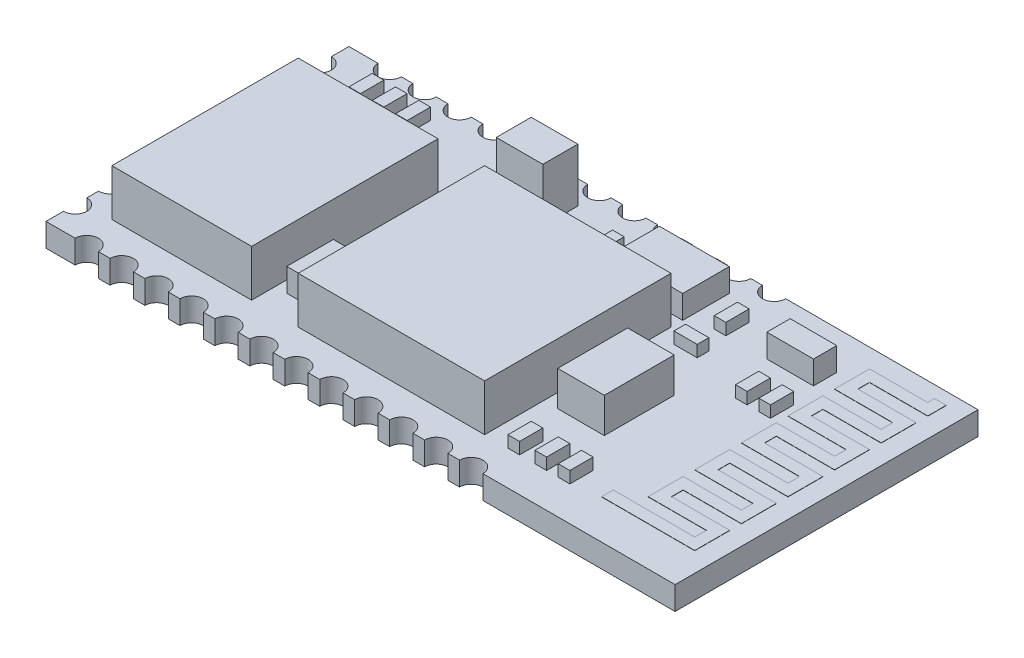
SolidWorks part; units mm, degrees
ref_plane "Front Plane" through (0, 0, 0) normal (0, 0, 1) x (1, 0, 0)
ref_plane "Top Plane" through (0, 0, 0) normal (0, 1, 0) x (1, 0, 0)
ref_plane "Right Plane" through (0, 0, 0) normal (1, 0, 0) x (0, 0, -1)
sketch "Sketch1" plane through (0, 0, 0) normal (0, 1, 0) x (1, 0, 0)
  line L1 (13.5, -6.5) -> (-13.5, -6.5)
  line L2 (13.5, -6.5) -> (13.5, 6.5)
  line L3 (13.5, 6.5) -> (-13.5, 6.5)
  line L4 (-13.5, -6.5) -> (-13.5, 6.5)
  line L5 (13.5, -6.5) -> (-13.5, 6.5) construction
  line L6 (13.5, 6.5) -> (-13.5, -6.5) construction
  point P0 (0, 0)
  dimension "D1" = 13
  dimension "D2" = 27
extrude "Boss-Extrude1" add sketch "Sketch1" along normal blind 1
sketch "Sketch2" plane through (0, 1, 0) normal (0, 1, 0) x (1, 0, 0)
  line L0 (-13.5, 6.5) -> (-13.5, -6.5) construction
  circle A0 centre (-13.5, 5.25) radius 0.5
  circle A1 centre (-13.5, 3.75) radius 0.5
  circle A2 centre (-13.5, 2.25) radius 0.5
  circle A3 centre (-13.5, 0.75) radius 0.5
  circle A4 centre (-13.5, -0.75) radius 0.5
  circle A5 centre (-13.5, -2.25) radius 0.5
  circle A6 centre (-13.5, -3.75) radius 0.5
  circle A7 centre (-13.5, -5.25) radius 0.5
  dimension "D1" = 1.25
  dimension "D2" = 2.75
  dimension "D3" = 4.25
  dimension "D4" = 5.75
  dimension "D5" = 7.25
  dimension "D6" = 8.75
  dimension "D7" = 10.25
  dimension "D8" = 11.75
extrude "Cut-Extrude7" cut sketch "Sketch2" against normal blind 2
sketch "Sketch9" plane through (0, 1, 0) normal (0, 1, 0) x (1, 0, 0)
  line L0 (13.5, 6.5) -> (-13.5, 6.5) construction
  line L1 (13.5, 0) -> (-13.5, 0) construction
  line L2 (13.5, -6.5) -> (13.5, 6.5) construction
  line L3 (-13.5, 0.25) -> (-13.5, -0.25) construction
  line L4 (-13.5, 6.5) -> (-13.5, 5.75) construction
  circle A0 centre (-11.75, 6.5) radius 0.5
  circle A1 centre (-10.25, 6.5) radius 0.5
  circle A2 centre (-8.75, 6.5) radius 0.5
  circle A3 centre (-7.25, 6.5) radius 0.5
  circle A4 centre (-5.75, 6.5) radius 0.5
  circle A5 centre (-4.25, 6.5) radius 0.5
  circle A6 centre (-2.75, 6.5) radius 0.5
  circle A7 centre (-1.25, 6.5) radius 0.5
  circle A8 centre (0.25, 6.5) radius 0.5
  circle A9 centre (1.75, 6.5) radius 0.5
  circle A10 centre (3.25, 6.5) radius 0.5
  circle A11 centre (4.75, 6.5) radius 0.5
  circle A12 centre (4.75, -6.5) radius 0.5
  circle A13 centre (3.25, -6.5) radius 0.5
  circle A14 centre (1.75, -6.5) radius 0.5
  circle A15 centre (0.25, -6.5) radius 0.5
  circle A16 centre (-1.25, -6.5) radius 0.5
  circle A17 centre (-2.75, -6.5) radius 0.5
  circle A18 centre (-4.25, -6.5) radius 0.5
  circle A19 centre (-5.75, -6.5) radius 0.5
  circle A20 centre (-7.25, -6.5) radius 0.5
  circle A21 centre (-8.75, -6.5) radius 0.5
  circle A22 centre (-10.25, -6.5) radius 0.5
  circle A23 centre (-11.75, -6.5) radius 0.5
  point P13 (0, 0)
  dimension "D1" = 1.75
  dimension "D2" = 1
  dimension "D3" = 12
  dimension "D4" = 1.5
extrude "Cut-Extrude9" cut sketch "Sketch9" against normal blind 2
sketch "Sketch10" plane through (0, 1, 0) normal (0, 1, 0) x (1, 0, 0)
  line L1 (-12.1586, 2.9835) -> (-6.1586, 2.9835)
  line L2 (-12.1586, 2.9835) -> (-12.1586, -5.0165)
  line L3 (-12.1586, -5.0165) -> (-6.1586, -5.0165)
  line L4 (-6.1586, 2.9835) -> (-6.1586, -5.0165)
  line L5 (-4.1586, 2.9835) -> (3.8414, 2.9835)
  line L6 (-4.1586, 2.9835) -> (-4.1586, -5.0165)
  line L7 (-4.1586, -5.0165) -> (3.8414, -5.0165)
  line L8 (3.8414, 2.9835) -> (3.8414, -5.0165)
  dimension "D1" = 6
  dimension "D2" = 8
  dimension "D3" = 2
  dimension "D4" = 8
  dimension "D5" = 2
extrude "Boss-Extrude2" add sketch "Sketch10" along normal blind 2
sketch "Sketch12" plane through (0, 1, 0) normal (0, 1, 0) x (1, 0, 0)
  line L0 (3.8414, 2.9835) -> (-4.1586, 2.9835) construction
  line L1 (0.8414, 5.4835) -> (3.8414, 5.4835)
  line L2 (0.8414, 5.4835) -> (0.8414, 3.4835)
  line L3 (0.8414, 3.4835) -> (3.8414, 3.4835)
  line L4 (3.8414, 5.4835) -> (3.8414, 3.4835)
  line L6 (3.8414, -5.0165) -> (3.8414, 2.9835) construction
  dimension "D1" = 2
  dimension "D2" = 3
  dimension "D3" = 0.5
  dimension "D4" = 0
extrude "Boss-Extrude3" add sketch "Sketch12" along normal blind 1
sketch "Sketch13" plane through (0, 1, 0) normal (0, 1, 0) x (1, 0, 0)
  line L1 (-4.6586, 5.4835) -> (-2.6586, 5.4835)
  line L2 (-4.6586, 5.4835) -> (-4.6586, 3.9835)
  line L3 (-4.6586, 3.9835) -> (-2.6586, 3.9835)
  line L4 (-2.6586, 5.4835) -> (-2.6586, 3.9835)
  line L5 (0.8414, 5.4835) -> (0.8414, 3.4835) construction
  line L7 (3.8414, 2.9835) -> (-4.1586, 2.9835) construction
  point P9 (0.8414, 4.4835)
  dimension "D1" = 1.5
  dimension "D2" = 2
  dimension "D3" = 3.5
  dimension "D4" = 1
extrude "Boss-Extrude4" add sketch "Sketch13" along normal blind 2.3
sketch "Sketch14" plane through (0, 1, 0) normal (0, 1, 0) x (1, 0, 0)
  line L0 (-13.5, 6.5) -> (-13.5, 5.75) construction
  line L1 (-11, 4.5) -> (-11.5, 4.5)
  line L2 (-11, 4.5) -> (-11, 5.5)
  line L3 (-11, 5.5) -> (-11.5, 5.5)
  line L4 (-11.5, 4.5) -> (-11.5, 5.5)
  line L5 (-10, 4.5) -> (-10, 5.5)
  line L6 (-10.5, 4.5) -> (-10.5, 5.5)
  line L7 (-10, 4.5) -> (-10.5, 4.5)
  line L8 (-9.5, 4.5) -> (-9.5, 5.5)
  line L9 (-9, 4.5) -> (-9.5, 4.5)
  line L10 (-9, 4.5) -> (-9, 5.5)
  line L11 (-9, 5.5) -> (-9.5, 5.5)
  line L12 (6.5, -5.0165) -> (6.5, -4.0165)
  line L13 (7.5, -5.0165) -> (7.5, -4.0165)
  line L14 (7.5, -4.0165) -> (7, -4.0165)
  line L15 (6.5, -4.0165) -> (6, -4.0165)
  line L16 (6.5, -5.0165) -> (6, -5.0165)
  line L17 (7.5, -5.0165) -> (7, -5.0165)
  line L18 (7, -5.0165) -> (7, -4.0165)
  line L19 (6, -5.0165) -> (6, -4.0165)
  line L20 (5.3414, -5.0165) -> (4.8414, -5.0165)
  line L21 (5.3414, -5.0165) -> (5.3414, -4.0165)
  line L22 (4.8414, -5.0165) -> (4.8414, -4.0165)
  line L23 (5.3414, -4.0165) -> (4.8414, -4.0165)
  line L24 (9.3661, 2.7256) -> (8.8661, 2.7256)
  line L25 (9.3661, 1.7256) -> (8.8661, 1.7256)
  line L26 (8.8661, 1.7256) -> (8.8661, 2.7256)
  line L27 (9.3661, 1.7256) -> (9.3661, 2.7256)
  line L28 (8.3661, 1.7256) -> (8.3661, 2.7256)
  line L29 (8.3661, 1.7256) -> (7.8661, 1.7256)
  line L30 (7.8661, 1.7256) -> (7.8661, 2.7256)
  line L31 (8.3661, 2.7256) -> (7.8661, 2.7256)
  line L32 (-5.4086, 2.5) -> (-5.4086, 3.5)
  line L33 (-4.9086, 2.5) -> (-5.4086, 2.5)
  line L34 (-4.9086, 3.5) -> (-5.4086, 3.5)
  line L35 (-4.9086, 2.5) -> (-4.9086, 3.5)
  line L36 (13.5, -6.5) -> (13.5, 6.5) construction
  line L38 (3.8414, -5.0165) -> (3.8414, 2.9835) construction
  line L39 (4.8414, 3.8366) -> (4.8414, 4.8366)
  line L40 (-4.9086, 0.5) -> (-5.4086, 0.5)
  line L41 (-5.4086, -0.5) -> (-5.4086, 0.5)
  line L42 (-4.9086, -0.5) -> (-4.9086, 0.5)
  line L43 (-4.9086, -0.5) -> (-5.4086, -0.5)
  line L44 (-4.9086, -4.1379) -> (-4.9086, -2.6379)
  line L45 (-4.9086, -2.6379) -> (-5.4086, -2.6379)
  line L46 (-5.4086, -4.1379) -> (-5.4086, -2.6379)
  line L47 (-4.9086, -4.1379) -> (-5.4086, -4.1379)
  line L48 (-6.1586, -5.0165) -> (-6.1586, 2.9835) construction
  line L49 (5.3414, 4.8366) -> (4.8414, 4.8366)
  line L50 (5.3414, 3.8366) -> (5.3414, 4.8366)
  line L51 (5.3414, 3.8366) -> (4.8414, 3.8366)
  line L52 (-0.0202, 3.8366) -> (-0.5202, 3.8366)
  line L53 (-0.0202, 4.8366) -> (-0.5202, 4.8366)
  line L54 (-0.0202, 3.8366) -> (-0.0202, 4.8366)
  line L55 (-0.5202, 3.8366) -> (-0.5202, 4.8366)
  line L56 (7.5, 4.196) -> (7.5, 3.696)
  line L57 (9, 3.696) -> (7.5, 3.696)
  line L58 (9, 4.196) -> (7.5, 4.196)
  line L59 (9, 4.196) -> (9, 3.696)
  line L60 (5.5459, 2.9031) -> (4.5459, 2.9031)
  line L61 (4.5459, -0.6918) -> (5.5459, -0.6918)
  line L62 (4.5459, -0.6918) -> (4.5459, -2.6918)
  line L63 (4.5459, -2.6918) -> (5.5459, -2.6918)
  line L64 (5.5459, -0.6918) -> (5.5459, -2.6918)
  line L65 (5.5459, 2.4031) -> (4.5459, 2.4031)
  line L66 (4.5459, 2.9031) -> (4.5459, 2.4031)
  line L67 (5.5459, 2.9031) -> (5.5459, 2.4031)
  line L68 (-10.5, 5.5) -> (-10, 5.5)
  line L69 (-9.5, 5.5) -> (-9, 5.5)
  dimension "D1" = 0.5
  dimension "D2" = 1
  dimension "D3" = 2
  dimension "D4" = 1
  dimension "D5" = 1
  dimension "D6" = 0.5
  dimension "D7" = 1
  dimension "D8" = 0.5
  dimension "D9" = 0.5
  dimension "D10" = 0.5
  dimension "D11" = 0.5
  dimension "D12" = 1
  dimension "D13" = 0.5
  dimension "D14" = 0.75
  dimension "D15" = 1
  dimension "D16" = 1
  dimension "D17" = 0.5
  dimension "D18" = 1
  dimension "D19" = 0.5
  dimension "D20" = 6
  dimension "D21" = 0.75
  dimension "D22" = 0.75
  dimension "D24" = 1
  dimension "D25" = 2
  dimension "D26" = 1
  dimension "D27" = 1.5
  dimension "D28" = 1
  dimension "D29" = 2
extrude "Boss-Extrude6" add sketch "Sketch14" along normal blind 0.5 contours L10 L11 L8 L9 | L43 L42 L40 L41 | L51 L50 L49 L39 | L28 L31 L30 L29 | L25 L27 L24 L26 | L19 L16 L12 L15 | L2 L3 L4 L1 | L6 L68 L5 L7 | L54 L53 L55 L52 | L32 L34 L35 L33 | L60 L66 L65 L67 | L18 L14 L13 L17 | L21 L23 L22 L20 region at (-9.25, 1, -5) region at (6.25, 1, 4.5165) region at (9.1161, 1, -2.2256) region at (8.1161, 1, -2.2256) region at (5.0914, 1, -4.3366) region at (-5.1586, 1, 0)
sketch "Sketch15" plane through (0, 1, 0) normal (0, 1, 0) x (1, 0, 0)
  line L0 (7.0844, 3.8532) -> (7.0844, 4.8532)
  line L1 (-5.6604, -2.0048) -> (-4.6604, -2.0048)
  line L2 (-5.6604, -2.0048) -> (-5.6604, -4.0048)
  line L3 (-5.6604, -4.0048) -> (-4.6604, -4.0048)
  line L4 (-4.6604, -2.0048) -> (-4.6604, -4.0048)
  line L5 (7.0844, 3.8532) -> (9.0844, 3.8532)
  line L6 (7.0844, 4.8532) -> (9.0844, 4.8532)
  line L7 (9.0844, 3.8532) -> (9.0844, 4.8532)
  dimension "D1" = 1
  dimension "D2" = 2
  dimension "D3" = 1
  dimension "D4" = 2
extrude "Boss-Extrude7" add sketch "Sketch15" along normal blind 1
sketch "Sketch16" plane through (0, 1, 0) normal (0, 1, 0) x (1, 0, 0)
  line L1 (4.4442, 0.5186) -> (6.4442, 0.5186)
  line L2 (4.4442, 0.5186) -> (4.4442, -2.4814)
  line L3 (4.4442, -2.4814) -> (6.4442, -2.4814)
  line L4 (6.4442, 0.5186) -> (6.4442, -2.4814)
  dimension "D1" = 2
  dimension "D2" = 3
extrude "Boss-Extrude8" add sketch "Sketch16" along normal blind 1.5
sketch "Sketch17" plane through (0, 1, 0) normal (0, 1, 0) x (1, 0, 0)
  line L0 (12.1639, 5.6806) -> (9.6639, 5.6806)
  line L1 (9.6639, 5.6806) -> (9.6639, 4.1806)
  line L2 (10.1639, 5.1806) -> (12.6639, 5.1806)
  line L3 (10.1639, 5.1806) -> (10.1639, 4.6806)
  line L4 (9.6639, 4.1806) -> (12.1639, 4.1806)
  line L5 (9.6639, 3.6806) -> (9.6639, 2.1806)
  line L6 (10.1639, 3.1806) -> (10.1639, 2.6806)
  line L7 (12.1639, 3.6806) -> (9.6639, 3.6806)
  line L8 (10.1639, 3.1806) -> (12.6639, 3.1806)
  line L9 (9.6639, 2.1806) -> (12.1639, 2.1806)
  line L10 (12.6639, 3.1806) -> (12.6639, 4.6806)
  line L11 (10.1639, 4.6806) -> (12.6639, 4.6806)
  line L12 (12.1639, 4.1806) -> (12.1639, 3.6806)
  line L13 (10.1639, 2.6806) -> (12.6639, 2.6806)
  line L14 (9.6639, 1.6806) -> (9.6639, 0.1806)
  line L15 (10.1639, -0.8194) -> (12.6639, -0.8194)
  line L16 (12.1639, 0.1806) -> (12.1639, -0.3194)
  line L17 (9.6639, -0.3194) -> (9.6639, -1.8194)
  line L18 (9.6639, 0.1806) -> (12.1639, 0.1806)
  line L19 (9.6639, -1.8194) -> (12.1639, -1.8194)
  line L20 (10.1639, -0.8194) -> (10.1639, -1.3194)
  line L21 (12.6639, -0.8194) -> (12.6639, 0.6806)
  line L22 (10.1639, 1.1806) -> (12.6639, 1.1806)
  line L23 (12.1639, -0.3194) -> (9.6639, -0.3194)
  line L24 (12.1639, 1.6806) -> (9.6639, 1.6806)
  line L25 (10.1639, 0.6806) -> (12.6639, 0.6806)
  line L26 (10.1639, -1.3194) -> (12.6639, -1.3194)
  line L27 (10.1639, 1.1806) -> (10.1639, 0.6806)
  line L28 (12.1639, 1.6806) -> (12.1639, 2.1806)
  line L29 (12.6639, 2.6806) -> (12.6639, 1.1806)
  line L30 (12.6639, -2.8194) -> (12.6639, -1.3194)
  line L31 (9.6639, -3.8194) -> (12.1639, -3.8194)
  line L32 (10.1639, -3.3194) -> (12.6639, -3.3194)
  line L33 (10.1639, -2.8194) -> (12.6639, -2.8194)
  line L34 (12.1639, -2.3194) -> (9.6639, -2.3194)
  line L35 (12.1639, -1.8194) -> (12.1639, -2.3194)
  line L36 (9.6639, -2.3194) -> (9.6639, -3.8194)
  line L37 (10.1639, -2.8194) -> (10.1639, -3.3194)
  line L38 (8.6639, -4.8194) -> (12.6639, -4.8194)
  line L39 (12.1639, -3.8194) -> (12.1639, -4.3194)
  line L40 (12.1639, -4.3194) -> (8.6639, -4.3194)
  line L41 (12.6639, -4.8194) -> (12.6639, -3.3194)
  line L42 (8.6639, -4.8194) -> (8.6639, -4.3194)
  line L43 (12.6639, 5.1806) -> (12.6639, 5.975)
  line L44 (12.6639, 5.975) -> (12.1639, 5.975)
  line L45 (12.1639, 5.975) -> (12.1639, 5.6806)
  dimension "D1" = 2.5
  dimension "D3" = 2.5
  dimension "D4" = 0.5
  dimension "D5" = 0.5
  dimension "D6" = 0.5
  dimension "D7" = 2.5
  dimension "D8" = 2.5
  dimension "D9" = 0.5
  dimension "D10" = 1.5
  dimension "D11" = 0.5
  dimension "D12" = 2.5
  dimension "D13" = 1.5
  dimension "D14" = 2.5
  dimension "D15" = 0.5
  dimension "D16" = 0.5
  dimension "D17" = 0.5
  dimension "D18" = 2.5
  dimension "D19" = 2.5
  dimension "D20" = 0.5
  dimension "D21" = 1.5
  dimension "D22" = 0.5
  dimension "D23" = 0.5
  dimension "D24" = 2.5
  dimension "D25" = 1.5
  dimension "D26" = 0.5
  dimension "D27" = 0.5
  dimension "D28" = 4
  dimension "D29" = 1.5
  dimension "D30" = 0.5
  dimension "D31" = 0.5
  dimension "D32" = 3.5
extrude "Boss-Extrude9" add sketch "Sketch17" along normal blind 0.01
